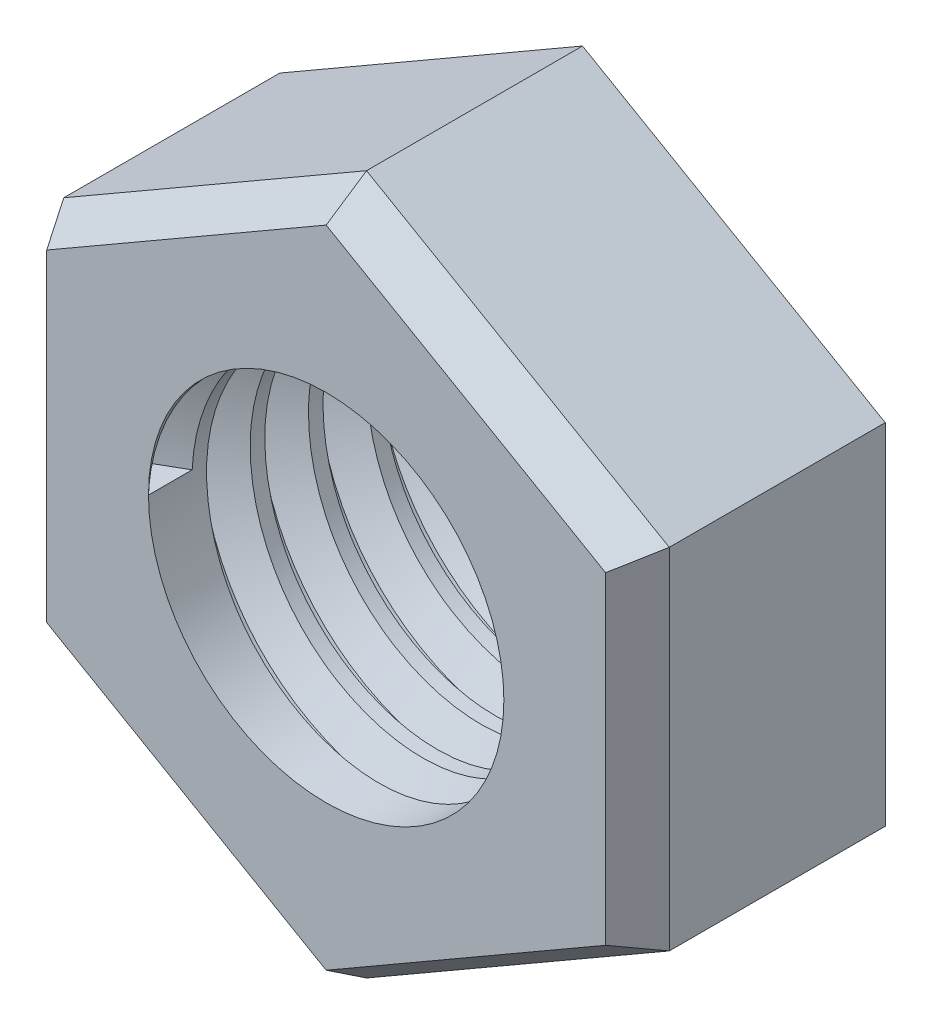
SolidWorks part; units mm, degrees
ref_plane "Спереди XY" through (0, 0, 0) normal (0, 0, 1) x (1, 0, 0)
ref_plane "Сверху XZ" through (0, 0, 0) normal (0, 1, 0) x (1, 0, 0)
ref_plane "Справа ZY" through (0, 0, 0) normal (1, 0, 0) x (0, 0, -1)
sketch "Эскиз2" plane through (0, 0, 0) normal (0, 0, 1) x (1, 0, 0)
  line L1 (0, 3) -> (-2.5981, 1.5)
  line L2 (-2.5981, 1.5) -> (-2.5981, -1.5)
  line L3 (-2.5981, -1.5) -> (0, -3)
  line L4 (0, -3) -> (2.5981, -1.5)
  line L5 (2.5981, -1.5) -> (2.5981, 1.5)
  line L6 (2.5981, 1.5) -> (0, 3)
  circle A0 centre (0, 0) radius 2.5981 construction
  dimension "D1" = 6
  dimension "D2" = 5.1962
extrude "Бобышка-Вытянуть1" add sketch "Эскиз2" along normal blind 2.4
sketch "Эскиз3" plane through (0, 0, 2.4) normal (0, 0, 1) x (1, 0, 0)
  circle A0 centre (0, 0) radius 1.525
  dimension "D1" = 3.05
extrude "Вырез-Вытянуть2" cut sketch "Эскиз3" against normal through all contours A0
thread "Резьба2" pitch 0.5 start angle 0, offset 0, length 2.4, pitch 0.5, diameter 3.05
ref_plane "Плоскость2" through (-1.525, 0, 2.4) normal (0, -1, 0) x (-1, 0, 0)
sketch "Профиль резьбы2" plane through (-1.525, 0, 2.4) normal (0, -1, 0) x (-1, 0, 0)
  line L0 (0, 0) -> (0, 0.5) construction
  line L1 (0, 0) -> (0.2706, 0.1562)
  line L2 (0.2706, 0.1562) -> (0.2706, 0.2187)
  line L3 (0.2706, 0.2187) -> (0, 0.375)
  line L4 (0.2706, 0.1875) -> (0, 0.1875) construction
  line L11 (0, 0) -> (0, 0.375)
  point P2 (0, 0)
  dimension "Pitch" = 0.5
  dimension "Profile_Angle" = 60
  dimension "Profile_Land" = 0.0625
  dimension "Profile_Height" = 0.2706
chamfer "Фаска1" distance 0.2 angle 60 12 edges at (1.299, -2.25, 2.4) (2.5981, 0, 2.4) (1.299, 2.25, 2.4) (-1.299, -2.25, 2.4) (-2.5981, 0, 2.4) (-1.299, 2.25, 2.4) (1.299, 2.25, 0) (2.5981, 0, 0) (1.299, -2.25, 0) (-1.299, -2.25, 0) (-2.5981, 0, 0) (-1.299, 2.25, 0)
